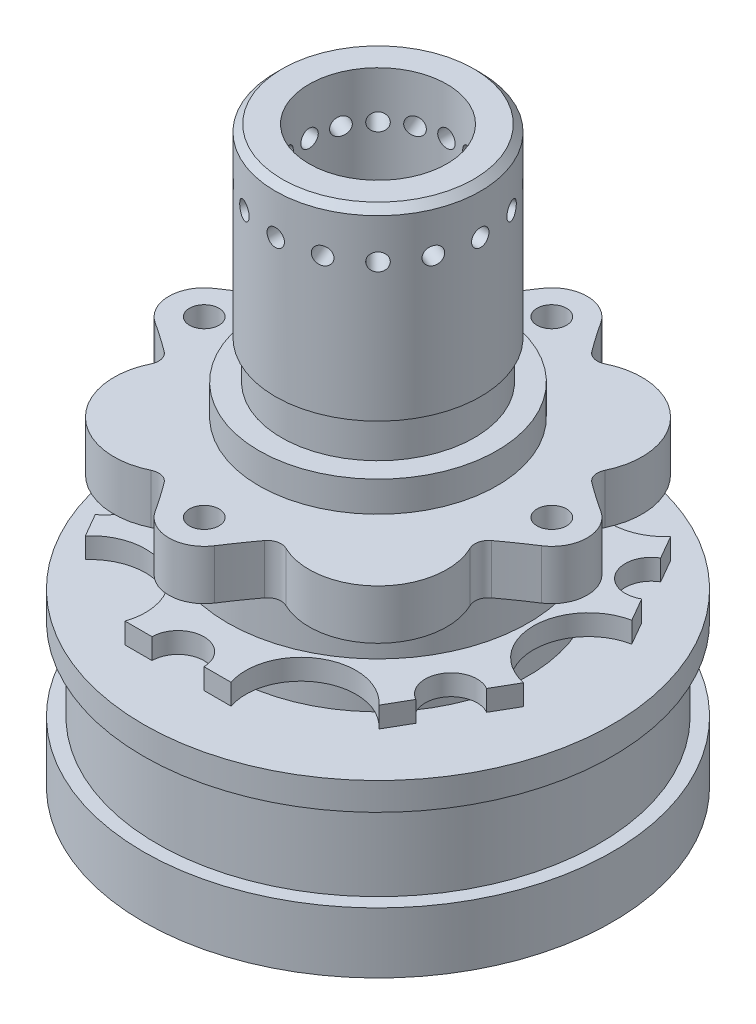
SolidWorks part; units mm, degrees
material "7075-T6 (SN)"
ref_plane "X-Y Datum" through (0, 0, 0) normal (0, 0, 1) x (1, 0, 0)
ref_plane "X-Z Datum" through (0, 0, 0) normal (0, 1, 0) x (1, 0, 0)
ref_plane "Y-Z Datum" through (0, 0, 0) normal (1, 0, 0) x (0, 0, -1)
sketch "Sketch1" plane through (0, 0, 0) normal (1, 0, 0) x (0, 0, -1)
  line L0 (0, 0) -> (-50000, 0) construction
  line L1 (0, 0) -> (0, 50000) construction
  line L2 (0, 0) -> (-34.6075, 0)
  line L8 (0, -62.23) -> (0, 0)
  line L10 (-34.6075, -17.0815) -> (-34.6075, -22.86)
  line L12 (-47.625, -12.319) -> (-47.625, -17.0815)
  line L13 (-47.625, -17.0815) -> (-34.6075, -17.0815)
  line L14 (-47.625, -12.319) -> (-34.6075, -12.319)
  line L15 (-34.6075, 0) -> (-34.6075, -12.319)
  line L16 (-34.6075, -22.86) -> (-53.975, -22.86)
  line L17 (-53.975, -22.86) -> (-53.975, -29.21)
  line L18 (-53.975, -29.21) -> (-50.8, -29.21)
  line L20 (-53.975, -62.23) -> (0, -62.23)
  line L21 (-50.8, -29.21) -> (-50.8, -48.26)
  line L22 (-50.8, -48.26) -> (-53.975, -48.26)
  line L23 (-53.975, -48.26) -> (-53.975, -62.23)
  dimension "D1" = 12.319
  dimension "D2" = 62.23
  dimension "D4" = 47.625
  dimension "D5" = 39.37
  dimension "D6" = 33.02
  dimension "D7" = 69.215
  dimension "D8" = 53.975
  dimension "D9" = 4.7625
  dimension "D10" = 50.8
  dimension "D11" = 13.97
sketch "Sketch2" plane through (0, 0, 0) normal (1, 0, 0) x (0, 0, -1)
  line L0 (0, 0) -> (-52.5, 0)
  line L1 (200000, 0) -> (-250000, 0) construction
  line L2 (-52.5, 0) -> (-52.5, 11.43)
  line L3 (-52.5, 11.43) -> (-27.4096, 11.43)
  line L4 (-27.4096, 11.43) -> (-27.4096, 18.43)
  line L5 (-27.4096, 18.43) -> (-22.225, 18.43)
  line L6 (-22.225, 18.43) -> (-22.225, 27.305)
  line L7 (-22.225, 27.305) -> (-23.6195, 27.305)
  line L10 (0, -200000) -> (0, 250000) construction
  line L11 (0, 69.85) -> (0, 0)
  line L15 (0, 69.85) -> (-22.032, 69.85)
  line L16 (-22.032, 69.85) -> (-23.6195, 68.2625)
  line L17 (-23.6195, 68.2625) -> (-23.6195, 27.305)
  line L18 (0, 0) -> (-50000, 0) construction
  line L19 (0, 0) -> (0, 50000) construction
  line L20 (0, 0) -> (0, -31242.0183) construction
  dimension "D1" = 11.43
  dimension "D2" = 58.42
  dimension "D3" = 47.2389
  dimension "D4" = 1.5875
  dimension "D5" = 45
  dimension "D6" = 54.8192
  dimension "D7" = 105
  dimension "D8" = 7
  dimension "D9" = 40.9575
  dimension "D10" = 44.45
revolve "Bearing Shaft/Flange Support" add sketch "Sketch1" angle 360 about L1
revolve "Drive Pin Support" add sketch "Sketch2" angle 360 about L19
sketch "Sketch5" plane through (0, 0, 0) normal (1, 0, 0) x (0, 0, -1)
  line L0 (0, 69.85) -> (15.875, 69.85)
  line L1 (22.032, 69.85) -> (-22.032, 69.85) construction
  line L5 (0, -62.23) -> (0, 69.85)
  line L6 (0, 0) -> (-50000, 0) construction
  line L7 (15.875, -62.23) -> (15.875, 69.85)
  line L8 (0, 0) -> (0, -50000) construction
  line L10 (-53.975, -62.23) -> (53.975, -62.23) construction
  line L11 (0, -62.23) -> (15.875, -62.23)
  dimension "D4" = 31.75
revolve "Center Mass Removal" cut sketch "Sketch5" angle 360 about L8
hole_wizard "Drive Pin Holes" positions "Sketch6" profile "Sketch7" tap size "M8x1.25" standard "ANSI Metric" end condition through all
sketch "Sketch6" plane through (0, 0, 0) normal (0, -1, 0) x (-1, 0, 0)
  circle A0 centre (0, 0) radius 40 construction
  point P0 (0, -40)
  dimension "D1" = 80
sketch "Sketch7" plane through (0, 0, 40) normal (1, 0, 0) x (0, 0, -1)
  line L0 (0, 0) -> (0, 69.85)
  line L1 (0, 69.85) -> (3.4, 69.85)
  line L2 (3.4, 69.85) -> (3.4, 0)
  line L5 (3.4, 0) -> (0, 0)
  line L11 (0, -6.35) -> (0, 107.95) construction
  dimension "Thru Tap Drill Dia." = 6.8
  dimension "Thru Tap Drill Depth" = 69.85
cosmetic thread "Hole Thread1" parameters "D2"=8
pattern_circular "Drive Pin Holes Pattern" count 4 over 360 about axis through (0, 0, 0) along (0, 1, 0) of "Drive Pin Holes"
cosmetic thread "Hole Thread2" parameters "D2"=8
cosmetic thread "Hole Thread3" parameters "D2"=8
cosmetic thread "Hole Thread4" parameters "D2"=8
sketch "Sketch8" plane through (0, 0, 0) normal (0, -1, 0) x (1, 0, 0)
  line L0 (0, 0) -> (-64.0279, 64.0279) construction
  line L1 (0, 0) -> (0, 72.7145) construction
  arc A0 (6.8518, 44.4362) -> (-6.8518, 44.4362) centre (0, 40) ccw
  arc A1 (6.8518, 44.4362) -> (13.2749, 35.4052) centre (113.4583, 113.4583) ccw
  arc A2 (44.4362, -6.8518) -> (44.4362, 6.8518) centre (40, 0) ccw
  arc A3 (44.4362, -6.8518) -> (44.4362, 6.8518) centre (40, 0) ccw
  arc A5 (44.4362, -6.8518) -> (35.4052, -13.2749) centre (113.4583, -113.4583) ccw
  circle A7 centre (0, 40) radius 3.4 construction
  circle A8 centre (0, 0) radius 52.5 construction
  circle A9 centre (0, 0) radius 40 construction
  arc A10 (-6.8518, -44.4362) -> (6.8518, -44.4362) centre (0, -40) ccw
  arc A11 (-6.8518, -44.4362) -> (6.8518, -44.4362) centre (0, -40) ccw
  arc A13 (-44.4362, 6.8518) -> (-44.4362, -6.8518) centre (-40, 0) ccw
  arc A14 (-44.4362, 6.8518) -> (-44.4362, -6.8518) centre (-40, 0) ccw
  arc A15 (-44.4362, 6.8518) -> (-35.4052, 13.2749) centre (-113.4583, 113.4583) ccw
  arc A16 (6.8518, 44.4362) -> (-6.8518, 44.4362) centre (0, 40) ccw
  circle A17 centre (0, 0) radius 52.5
  arc A18 (-6.8518, -44.4362) -> (-13.2749, -35.4052) centre (-113.4583, -113.4583) ccw
  arc A19 (-169.6965, 0.4112) -> (0.4112, -169.6965) centre (-113.4583, -113.4583) ccw [skipped]
  arc A20 (-13.2749, 35.4052) -> (-35.4052, 13.2749) centre (-22.4506, 22.4506) ccw
  arc A21 (-13.2749, 35.4052) -> (-6.8518, 44.4362) centre (-113.4583, 113.4583) ccw
  arc A22 (35.4052, 13.2749) -> (13.2749, 35.4052) centre (22.4506, 22.4506) ccw
  arc A23 (13.2749, -35.4052) -> (35.4052, -13.2749) centre (22.4506, -22.4506) ccw
  arc A24 (-35.4052, -13.2749) -> (-13.2749, -35.4052) centre (-22.4506, -22.4506) ccw
  arc A25 (35.4052, 13.2749) -> (44.4362, 6.8518) centre (113.4583, 113.4583) ccw
  arc A26 (13.2749, -35.4052) -> (6.8518, -44.4362) centre (113.4583, -113.4583) ccw
  arc A27 (-35.4052, -13.2749) -> (-44.4362, -6.8518) centre (-113.4583, -113.4583) ccw
  point P49 (0, 0)
  circle M10 centre (0, 0) radius 52.5
  dimension "D1" = 4.7625
  dimension "D2" = 45
  dimension "D3" = 254
  dimension "D4" = 80
  dimension "D6" = 31.75
  dimension "D7" = 31.75
  dimension "D5" = 4
  dimension "D8" = 4
extrude "Flange Support Cut" cut sketch "Sketch8" against normal up to next contours A10 A18 A13 A15 A0 A1 A2 A5 M10
sketch "Sketch10" plane through (0, -12.319, 0) normal (0, -1, 0) x (1, 0, 0)
  line L0 (0, 0) -> (0, 50000) construction
  line L7 (0, 0) -> (50000, 0) construction
  line L8 (-5.969, -46.0335) -> (-12.2091, -46.0335)
  line L9 (5.969, -46.0375) -> (12.1938, -46.0375)
  line L10 (-42.8506, -17.8474) -> (-45.9707, -12.4434)
  line L11 (-36.8851, -28.1881) -> (-33.7727, -33.5789)
  line L12 (-36.8816, 28.186) -> (-33.7616, 33.5901)
  line L13 (-42.8541, 17.8494) -> (-45.9666, 12.4586)
  line L14 (5.969, 46.0335) -> (12.2091, 46.0335)
  line L15 (-5.969, 46.0375) -> (-12.1938, 46.0375)
  line L16 (42.8506, 17.8474) -> (45.9707, 12.4434)
  line L17 (36.8851, 28.1881) -> (33.7727, 33.5789)
  line L18 (36.8816, -28.186) -> (33.7616, -33.5901)
  line L19 (42.8541, -17.8494) -> (45.9666, -12.4586)
  arc A0 (-5.969, -46.0335) -> (5.969, -46.0375) centre (0, -46.0375) cw
  arc A1 (-42.8506, -17.8474) -> (-36.8851, -28.1881) centre (-39.8696, -23.0187) cw
  arc A3 (-36.8816, 28.186) -> (-42.8541, 17.8494) centre (-39.8696, 23.0188) cw
  circle A4 centre (0, 0) radius 47.625 construction
  arc A5 (5.969, 46.0335) -> (-5.969, 46.0375) centre (0, 46.0375) cw
  arc A6 (42.8506, 17.8474) -> (36.8851, 28.1881) centre (39.8696, 23.0187) cw
  arc A7 (36.8816, -28.186) -> (42.8541, -17.8494) centre (39.8696, -23.0188) cw
  circle A8 centre (0, 0) radius 47.625
  arc A9 (-33.7727, -33.5789) -> (-12.2091, -46.0335) centre (-24.2426, -41.9733) cw
  arc A10 (-45.9666, 12.4586) -> (-45.9707, -12.4434) centre (-48.4712, 0.008) cw
  arc A11 (-12.1938, 46.0375) -> (-33.7616, 33.5901) centre (-24.2287, 41.9813) cw
  arc A12 (33.7727, 33.5789) -> (12.2091, 46.0335) centre (24.2426, 41.9733) cw
  arc A13 (45.9666, -12.4586) -> (45.9707, 12.4434) centre (48.4712, -0.008) cw
  arc A14 (12.1938, -46.0375) -> (33.7616, -33.5901) centre (24.2287, -41.9813) cw
  point P42 (0, 0)
  point P60 (0, 0)
  dimension "D2" = 5.969
  dimension "D1" = 46.0375
  dimension "D5" = 95.25
  dimension "D6" = 12.7
  dimension "D3" = 6.2401
  dimension "D8" = 46.0375
  dimension "D4" = 6
  dimension "D7" = 6
extrude "Brake Hat Hex" cut sketch "Sketch10" along direction (0, -1, 0) on the side of the normal up to surface (4.7625 mm away)
fillet "Hub Fillet" [suppressed] radius 0.7937
sketch "Sketch14" plane through (0, 0, 0) normal (1, 0, 0) x (0, 0, -1)
  line L0 (22.032, 69.85) -> (-22.032, 69.85) construction
  line L1 (0, 0) -> (-50000, 0) construction
  line L2 (0, 0) -> (0, -50000) construction
  circle A0 centre (0, 59.05) radius 2
  dimension "D2" = 4
  dimension "D1" = 10.8
extrude "Pin Holes" cut sketch "Sketch14" against normal through all
pattern_circular "Pin Hole Pattern" count 16 over 360 about axis through (0, 0, 0) along (0, -1, 0) of "Pin Holes"
chamfer "Floral Pattern Chamfer" [suppressed] distance 3.175 angle 45
thread "Main Big Threads" [suppressed] pitch 2.1167 start angle 0, offset 0.3048, length 0, pitch 2.1167, diameter 47.625
ref_plane "Plane1" through (-23.8125, 70.1548, 0) normal (0, 0, 1) x (-1, 0, 0)
sketch "Thread Profile1" plane through (-23.8125, 70.1548, 0) normal (0, 0, 1) x (-1, 0, 0)
  line L0 (0, 0) -> (0, 2.1167) construction
  line L11 (0, 0) -> (0, 1.8521)
  line L12 (0, 1.8521) -> (-1.1457, 1.1906)
  line L13 (-1.1457, 1.1906) -> (-1.1457, 0.6615)
  line L15 (-1.1457, 0.6615) -> (0, 0)
  line L17 (-1.1457, 0.926) -> (0, 0.926) construction
  point P2 (0, 0)
  dimension "Pitch" = 2.1167
  dimension "Profile_Angle" = 60
  dimension "Profile_Land" = 0.5292
  dimension "Profile_Height" = 1.1457
fillet "Fillet1" radius 3.175 8 edges at (-13.2749, 5.715, 35.4052) (-35.4052, 5.715, 13.2749) (-35.4052, 5.715, -13.2749) (-13.2749, 5.715, -35.4052) (13.2749, 5.715, -35.4052) (35.4052, 5.715, -13.2749) (35.4052, 5.715, 13.2749) (13.2749, 5.715, 35.4052)
sketch "Sketch17" plane through (0, -62.23, 0) normal (0, -1, 0) x (1, 0, 0)
  circle A0 centre (0, 39.1583) radius 8.7312
  circle A1 centre (33.9121, -19.5792) radius 8.7313
  circle A2 centre (-33.9121, -19.5792) radius 8.7313
  point P9 (0, 0)
  dimension "D1" = 17.4625
  dimension "D3" = 39.1583
  dimension "D2" = 3
extrude "Cut-Extrude1" cut sketch "Sketch17" against normal blind 7.9375
sketch "Sketch18" plane through (0, -54.2925, 0) normal (0, -1, 0) x (1, 0, 0)
  circle A0 centre (0, 39.1583) radius 6.7469
  circle A1 centre (0, 39.1583) radius 8.7312
  circle A2 centre (0, 39.1583) radius 8.7312 construction
  circle A3 centre (33.9121, -19.5792) radius 6.7469
  circle A4 centre (-33.9121, -19.5792) radius 6.7469
  point P10 (0, 0)
  dimension "D2" = 13.4937
  dimension "D1" = 0
  dimension "D3" = 3
extrude "Cut-Extrude2" cut sketch "Sketch18" against normal blind 1.27
sketch "Sketch20" plane through (0, -53.0225, 0) normal (0, -1, 0) x (1, 0, 0)
  circle A0 centre (0, 39.1583) radius 6.7469 construction
  circle A1 centre (0, 39.1583) radius 6.7469
  point P0 (0, 39.1583)
hole_wizard "1/4-20 Tapped Hole2" positions "Sketch20" profile "Sketch21" tap size "1/4-20" standard "ANSI Inch"
sketch "Sketch21" plane through (0, -53.0225, 39.1583) normal (1, 0, 0) x (0, 0, -1)
  line L0 (0, 0) -> (0, 25.6638)
  line L1 (0, 25.6638) -> (2.5527, 24.13)
  line L2 (2.5527, 24.13) -> (2.5527, 0)
  line L5 (2.5527, 0) -> (0, 0)
  line L10 (0, 25.6638) -> (-2.5527, 24.13) construction
  line L11 (0, -6.35) -> (0, 107.95) construction
  dimension "Tap Drill Dia." = 5.1054
  dimension "Tap Drill Depth" = 24.13
  dimension "Drill Angle" = 118
cosmetic thread "Hole Thread8" parameters "D1"=24.13, "D2"=6.35
pattern_circular "CirPattern2" count 3 over 360 about axis through (0, 0, 0) along (0, 1, 0) of "1/4-20 Tapped Hole2"
cosmetic thread "Hole Thread9" parameters "D1"=24.13, "D2"=6.35
cosmetic thread "Hole Thread10" parameters "D1"=24.13, "D2"=6.35
sketch "Sketch22" plane through (0, -62.23, 0) normal (0, -1, 0) x (1, 0, 0)
  line L0 (0, 0) -> (0, 53.975) construction
  line L1 (0, 0) -> (46.7437, -26.9875) construction
  circle A0 centre (0, 0) radius 53.975 construction
  arc A1 (21.2149, 39.0606) -> (44.4349, -1.1577) centre (0, 0) cw
  arc A2 (9.7736, 19.2511) -> (21.5587, -1.1613) centre (0, 0) cw
  arc A3 (8.4322, 29.6616) -> (12.1228, 35.3731) centre (0, 39.1583) ccw
  arc A4 (36.6954, -7.1879) -> (29.9037, -7.5283) centre (33.9121, -19.5792) ccw
  arc A5 (21.5587, -1.1613) -> (29.9037, -7.5283) centre (27.8996, -1.5029) ccw
  arc A6 (44.4349, -1.1577) -> (36.6954, -7.1879) centre (38.0871, -0.9923) cw
  arc A7 (21.2149, 39.0606) -> (12.1228, 35.3731) centre (18.1842, 33.4805) ccw
  arc A8 (9.7736, 19.2511) -> (8.4322, 29.6616) centre (12.6482, 24.9132) cw
  arc A9 (21.4716, -22.1332) -> (24.5726, -28.1852) centre (33.9121, -19.5792) ccw
  arc A10 (23.22, -37.9029) -> (24.5726, -28.1852) centre (19.9029, -32.4882) ccw
  arc A11 (23.22, -37.9029) -> (-23.22, -37.9029) centre (0, 0) cw
  arc A12 (-23.22, -37.9029) -> (-24.5726, -28.1852) centre (-19.9029, -32.4882) cw
  arc A13 (-24.5726, -28.1852) -> (-21.4716, -22.1332) centre (-33.9121, -19.5792) ccw
  arc A14 (11.7851, -18.0898) -> (-11.7851, -18.0898) centre (0, 0) cw
  arc A15 (-11.7851, -18.0898) -> (-21.4716, -22.1332) centre (-15.2513, -23.4103) ccw
  arc A16 (11.7851, -18.0898) -> (21.4716, -22.1332) centre (15.2513, -23.4103) cw
  arc A17 (-29.9037, -7.5283) -> (-36.6954, -7.1879) centre (-33.9121, -19.5792) ccw
  arc A18 (-44.4349, -1.1577) -> (-36.6954, -7.1879) centre (-38.0871, -0.9923) ccw
  arc A19 (-44.4349, -1.1577) -> (-21.2149, 39.0606) centre (0, 0) cw
  arc A20 (-21.2149, 39.0606) -> (-12.1228, 35.3731) centre (-18.1842, 33.4805) cw
  arc A21 (-12.1228, 35.3731) -> (-8.4322, 29.6616) centre (0, 39.1583) ccw
  arc A22 (-21.5587, -1.1613) -> (-9.7736, 19.2511) centre (0, 0) cw
  arc A23 (-9.7736, 19.2511) -> (-8.4322, 29.6616) centre (-12.6482, 24.9132) ccw
  arc A24 (-21.5587, -1.1613) -> (-29.9037, -7.5283) centre (-27.8996, -1.5029) cw
  point P53 (0, 0)
  dimension "D2" = 12.7
  dimension "D3" = 12.7
  dimension "D4" = 21.59
  dimension "D5" = 44.45
  dimension "D6" = 6.35
  dimension "D1" = 120
  dimension "D7" = 3
extrude "Cut-Extrude3" cut sketch "Sketch22" against normal blind 34.29
fillet "Fillet2" radius 6.35 24 edges at (0, -27.94, -21.59) (17.6975, -27.94, -17.5503) (22.6095, -27.94, -25.3706) (26.1923, -27.94, -33.3636) (0, -27.94, -44.45) (-26.1923, -27.94, -33.3636) (-22.6095, -27.94, -25.3706) (-17.6975, -27.94, -17.5503) (-18.6975, -27.94, 10.795) (-24.0478, -27.94, -6.5513) (-33.2764, -27.94, -6.8951) (-41.9899, -27.94, -6.0013) (-38.4948, -27.94, 22.225) (-15.7976, -27.94, 39.365) (-10.6669, -27.94, 32.2657) (-6.3503, -27.94, 24.1016) (18.6975, -27.94, 10.795) (6.3503, -27.94, 24.1016) (10.6669, -27.94, 32.2657) (15.7976, -27.94, 39.365) (38.4948, -27.94, 22.225) (41.9899, -27.94, -6.0013) (33.2764, -27.94, -6.8951) (24.0478, -27.94, -6.5513)
